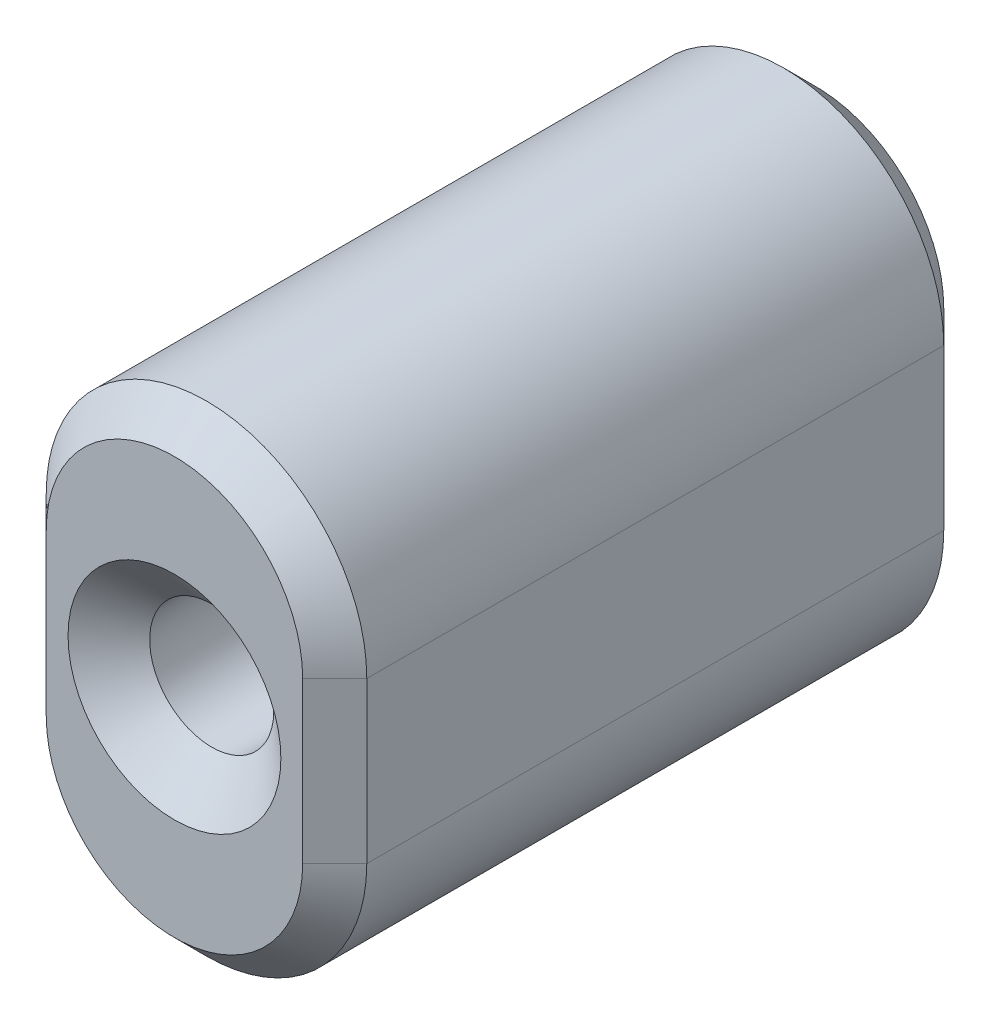
SolidWorks part; units mm, degrees
material "PET"
ref_plane "Front Plane" through (0, 0, 0) normal (0, 0, 1) x (1, 0, 0)
ref_plane "Top Plane" through (0, 0, 0) normal (0, 1, 0) x (1, 0, 0)
ref_plane "Right Plane" through (0, 0, 0) normal (1, 0, 0) x (0, 0, -1)
sketch "Sketch1" plane through (0, 0, 0) normal (0, 0, 1) x (1, 0, 0)
  line L0 (0, -3.175) -> (0, 3.175) construction
  line L1 (-6.35, -3.175) -> (-6.35, 3.175)
  line L2 (6.35, -3.175) -> (6.35, 3.175)
  arc A1 (-6.35, -3.175) -> (6.35, -3.175) centre (0, -3.175) ccw
  arc A2 (6.35, 3.175) -> (-6.35, 3.175) centre (0, 3.175) ccw
  point P3 (0, 0)
  dimension "D1" = 19.05
  dimension "D2" = 12.7
extrude "Boss-Extrude1" add sketch "Sketch1" along normal blind 25.4
chamfer "Chamfer1" distance 1.27 angle 45 8 edges at (6.35, 0, 0) (0, 9.525, 0) (-6.35, 0, 0) (0, -9.525, 0) (-6.35, 0, 25.4) (0, 9.525, 25.4) (6.35, 0, 25.4) (0, -9.525, 25.4)
hole_wizard "CSK for #8 Flat Head Machine Screw (100)1" positions "Sketch2" profile "Sketch3" countersink size "#8" standard "ANSI Inch" end condition through all
sketch "Sketch2" plane through (0, 0, 25.4) normal (0, 0, 1) x (1, 0, 0)
  point P0 (0, 0)
sketch "Sketch3" plane through (0, 0, 25.4) normal (1, 0, 0) x (0, -1, 0)
  line L0 (0, 0) -> (0, 25.4)
  line L1 (0, 25.4) -> (2.4574, 25.4)
  line L2 (2.4574, 25.4) -> (2.4574, 1.4759)
  line L3 (2.4574, 1.4759) -> (4.2164, 0)
  line L5 (4.2164, 0) -> (0, 0)
  line L6 (-2.4574, 1.4759) -> (-4.2164, 0) construction
  line L11 (0, -6.35) -> (0, 107.95) construction
  dimension "Thru Hole Dia." = 4.9149
  dimension "Thru Hole Depth" = 25.4
  dimension "Near C'Sink Dia." = 8.4328
  dimension "Near C'Sink Angle" = 100
